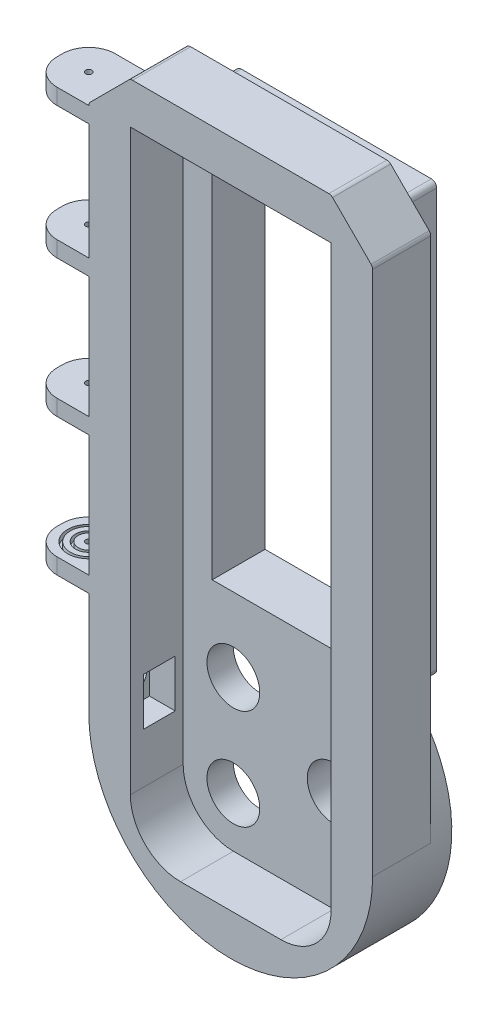
SolidWorks part; units mm, degrees
ref_plane "Alzado" through (0, 0, 0) normal (0, 0, 1) x (1, 0, 0)
ref_plane "Planta" through (0, 0, 0) normal (0, 1, 0) x (1, 0, 0)
ref_plane "Vista lateral" through (0, 0, 0) normal (1, 0, 0) x (0, 0, -1)
sketch "Croquis1" plane through (0, 0, 0) normal (0, 0, 1) x (1, 0, 0)
  line L1 (-19, -40.5) -> (19, -40.5)
  line L2 (-19, -40.5) -> (-19, 40.5)
  line L3 (-19, 40.5) -> (19, 40.5)
  line L4 (19, -40.5) -> (19, 40.5)
  line L5 (-19, -40.5) -> (19, 40.5) construction
  line L6 (-19, 40.5) -> (19, -40.5) construction
  line L7 (-19, -40.5) -> (19, -40.5)
  line L8 (-19, -40.5) -> (-19, -78.5)
  line L9 (-19, -78.5) -> (19, -78.5)
  line L10 (19, -40.5) -> (19, -78.5)
  line L13 (-13.5, 36) -> (13.5, 36)
  line L28 (13.5, 36) -> (13.5, -36)
  line L29 (-13.5, 36) -> (-13.5, -36)
  line L30 (-13.5, -36) -> (13.5, -36)
  circle A0 centre (-9.5, -50) radius 5
  circle A1 centre (9.5, -59.5) radius 5
  circle A2 centre (-9.5, -69) radius 5
  arc A3 (19, -40.5) -> (-19, -40.5) centre (0, -59.5) cw
  point P0 (0, 0)
  point P27 (9.5, -64.5)
  point P30 (9.5, -54.5)
  point P34 (-13.5, 0)
extrude "Saliente-Extruir1" add sketch "Croquis1" along normal blind 5 contours L1 L4 L3 L2 L30 L29 L13 L28 | L10 L1 L8 L9 A2 A1 A0 | A3 L10 | A3 L9 | A3 L8 region at (-18.1053, 0, 0) region at (0.6175, -59.5, 0) region at (-22.1912, -59.5, 0) region at (22.1912, -59.5, 0) region at (0, -81.6912, 0)
sketch "Croquis2" plane through (0, 0, 0) normal (0, 0, -1) x (-1, 0, 0)
  line L0 (-19, 40.5) -> (19, 40.5)
  line L1 (19, -40.5) -> (-19, -40.5)
  line L2 (-19, -40.5) -> (-19, 40.5)
  line L4 (19, -40.5) -> (19, 40.5)
  line L5 (-13.5, 36) -> (-13.5, -36)
  line L7 (-13.5, -36) -> (13.5, -36)
  line L8 (13.5, -36) -> (13.5, 36)
  line L9 (13.5, 36) -> (-13.5, 36)
extrude "Saliente-Extruir2" add sketch "Croquis2" along normal blind 5
sketch "Croquis3" plane through (0, 0, 5) normal (0, 0, 1) x (1, 0, 0)
  line L0 (26.8701, -59.5) -> (26.8701, 40.5)
  line L1 (19, -59.5) -> (19, 40.5)
  line L2 (19, 40.5) -> (-19, 40.5)
  line L3 (-19, 40.5) -> (-19, -59.5)
  line L4 (26.8701, 40.5) -> (19, 48.3701)
  line L5 (19, 48.3701) -> (-19, 48.3701)
  line L6 (-19, 48.3701) -> (-26.8701, 40.5)
  line L7 (-26.8701, 40.5) -> (-26.8701, -59.5)
  arc A2 (-19, -59.5) -> (19, -59.5) centre (0, -59.5) ccw
  arc A3 (-26.8701, -59.5) -> (26.8701, -59.5) centre (0, -59.5) ccw
extrude "Saliente-Extruir9" add sketch "Croquis3" against normal blind 1
sketch "Croquis4" plane through (0, 0, 4) normal (0, 0, -1) x (-1, 0, 0)
  line L0 (-19, 40.5) -> (-19, -40.5)
  line L1 (-19, 40.5) -> (19, 40.5)
  line L2 (19, 40.5) -> (19, -40.5)
  line L3 (14, -77) -> (-14, -77)
  line L4 (-19, -72) -> (-19, -41.338)
  line L5 (19, -72) -> (19, -40.5)
  line L6 (-26.8701, 40.5) -> (-19, 48.3701)
  line L7 (-19, 48.3701) -> (19, 48.3701)
  line L8 (19, 48.3701) -> (26.8701, 40.5)
  line L9 (26.8701, 40.5) -> (26.8701, -59.5)
  line L10 (-26.8701, 40.5) -> (-26.8701, -59.5)
  arc A0 (-19, -40.5) -> (-26.8701, -59.5) centre (0, -59.5) ccw construction
  arc A1 (-14, -77) -> (-19, -72) centre (-14, -72) cw
  arc A2 (14, -77) -> (19, -72) centre (14, -72) ccw
  arc A3 (-19, -40.5) -> (19, -40.5) centre (0, -59.5) ccw construction
  arc A4 (-26.8701, -59.5) -> (26.8701, -59.5) centre (0, -59.5) ccw
  arc M1 (19, -40.5) -> (26.8701, -59.5) centre (0, -59.5) cw
  line M2 (26.8701, -59.5) -> (26.8701, 40.5)
  line M3 (26.8701, 40.5) -> (19, 48.3701)
  line M4 (19, 48.3701) -> (-19, 48.3701)
  line M5 (-19, 48.3701) -> (-26.8701, 40.5)
  line M6 (-26.8701, 40.5) -> (-26.8701, -59.5)
  arc M7 (-26.8701, -59.5) -> (-19, -40.5) centre (0, -59.5) cw
  line M8 (-19, -40.5) -> (-19, 40.5)
  line M9 (-19, 40.5) -> (19, 40.5)
  line M10 (19, 40.5) -> (19, -40.5)
  dimension "D1" = 5
extrude "Saliente-Extruir10" add sketch "Croquis4" against normal blind 11 contours M10 M1 M2 M3 M4 M5 M6 M7 M8 M9 region at (20.2052, 0, 4)
sketch "Croquis5" plane through (0, 0, 5) normal (0, 0, 1) x (1, 0, 0)
  line L0 (-19, -59.5) -> (-19, -69)
  line L1 (19, -69) -> (19, -59.5)
  line L2 (9.5, -78.5) -> (-9.5, -78.5)
  line L3 (19, -59.5) -> (19, -40.5)
  line L4 (-19, -59.5) -> (-19, -40.5)
  arc A0 (-19, -40.5) -> (19, -40.5) centre (0, -59.5) ccw
  arc A1 (-9.5, -78.5) -> (-19, -69) centre (-9.5, -69) cw
  arc A2 (9.5, -78.5) -> (19, -69) centre (9.5, -69) ccw
extrude "Saliente-Extruir11" add sketch "Croquis5" along normal blind 10
fillet "Redondeo1" radius 1 4 edges at (-19, -40.5, -2.5) (-19, 40.5, -0.5) (19, 40.5, -0.5) (19, -40.5, -2.5)
fillet "Redondeo2" radius 1 5 edges at (-18.7071, 40.2071, 4) (18.7071, 40.2071, 4) (-19, -0.5, 4) (0, 40.5, 4) (19, -0.5, 4)
fillet "Redondeo3" radius 1 4 edges at (-26.8701, 40.5, 9.5) (-19, 48.3701, 9.5) (26.8701, 40.5, 9.5) (19, 48.3701, 9.5)
sketch "Croquis6" plane through (-26.8701, 0, 0) normal (-1, 0, 0) x (0, 0, 1)
  line L1 (4, -59.5) -> (15, -59.5) construction
  line L2 (6.5, -50.5) -> (12.5, -50.5)
  line L3 (12.5, -50.5) -> (12.5, -59.5)
  line L4 (12.5, -59.5) -> (6.5, -59.5)
  line L5 (6.5, -50.5) -> (6.5, -59.5)
extrude "Cortar-Extruir1" cut sketch "Croquis6" against normal blind 8
sketch "Croquis7" plane through (-26.8701, 0, 0) normal (-1, 0, 0) x (0, 0, 1)
  line L0 (6.5, -50.5) -> (12.5, -50.5)
  line L1 (12.5, -50.5) -> (12.5, -59.5)
  line L2 (12.5, -59.5) -> (6.5, -59.5)
  line L3 (6.5, -59.5) -> (6.5, -50.5)
  circle A0 centre (9.5, -55) radius 2.5
extrude "Saliente-Extruir12" add sketch "Croquis7" against normal blind 3
sketch "Croquis8" plane through (-26.8701, 0, 0) normal (-1, 0, 0) x (0, 0, 1)
  line L0 (4, 40.0858) -> (4, 37.0858)
  line L1 (4, 39.5) -> (4, -41.5556) construction
  line L2 (4, 37.0858) -> (15, 37.0858)
  line L3 (15, -59.5) -> (15, 40.0858) construction
  line L4 (15, 37.0858) -> (15, 40.0858)
  line L5 (15, 40.0858) -> (4, 40.0858)
  line L6 (9.5, 37.0858) -> (9.5, 15.0858)
  line L7 (9.5, 15.0858) -> (15, 15.0858)
  line L8 (9.5, 15.0858) -> (4, 15.0858)
  line L9 (4, 15.0858) -> (4, 12.0858)
  line L10 (4, 40.0858) -> (4, -59.5) construction
  line L11 (4, 12.0858) -> (15, 12.0858)
  line L12 (15, 12.0858) -> (15, 15.0858)
  line L13 (9.5, 12.0858) -> (9.5, -10.9142)
  line L14 (9.5, -10.9142) -> (15, -10.9142)
  line L15 (15, -10.9142) -> (15, -13.9142)
  line L16 (15, -13.9142) -> (4, -13.9142)
  line L17 (4, -13.9142) -> (4, -10.9142)
  line L18 (4, -10.9142) -> (9.5, -10.9142)
  line L19 (9.5, -13.9142) -> (9.5, -36.9142)
  line L20 (9.5, -36.9142) -> (15, -36.9142)
  line L21 (15, -36.9142) -> (15, -39.9142)
  line L22 (15, -39.9142) -> (4, -39.9142)
  line L23 (4, -39.9142) -> (4, -36.9142)
  line L24 (4, -36.9142) -> (9.5, -36.9142)
  line M2 (15, -59.5) -> (15, 40.0858)
  line M3 (15, 40.0858) -> (4, 40.0858)
  line M4 (4, 40.0858) -> (4, -59.5)
extrude "Saliente-Extruir13" add sketch "Croquis8" along normal blind 11 contours L2 M4 M2 M3 | L11 L7 L8 M4 M2 | L18 L16 L14 M4 M2 | L24 L22 L20 M4 M2 region at (-26.8701, 38.5858, 9.5) region at (-26.8701, 13.5858, 9.5) region at (-26.8701, -12.4142, 9.5) region at (-26.8701, -38.4142, 9.5)
fillet "Redondeo4" radius 5 8 edges at (-37.8701, -38.4142, 4) (-37.8701, -38.4142, 15) (-37.8701, -12.4142, 4) (-37.8701, -12.4142, 15) (-37.8701, 13.5858, 4) (-37.8701, 13.5858, 15) (-37.8701, 38.5858, 4) (-37.8701, 38.5858, 15)
sketch "Croquis9" plane through (0, 40.0858, 0) normal (0, 1, 0) x (1, 0, 0)
  circle A0 centre (-32.3701, -9.5) radius 0.6
extrude "Cortar-Extruir2" cut sketch "Croquis9" against normal blind 80
sketch "Croquis10" plane through (0, -39.9142, 0) normal (0, -1, 0) x (1, 0, 0)
  circle A0 centre (-32.3701, 9.5) radius 0.6
extrude "Saliente-Extruir14" add sketch "Croquis10" against normal blind 2
sketch "Croquis11" plane through (0, -36.9142, 0) normal (0, 1, 0) x (1, 0, 0)
  circle A0 centre (-32.3701, -9.5) radius 2
  circle A1 centre (-32.3701, -9.5) radius 2.5
  circle A2 centre (-32.3701, -9.5) radius 3.5
  circle A3 centre (-32.3701, -9.5) radius 4
extrude "Cortar-Extruir3" cut sketch "Croquis11" against normal blind 1 contours A3 A2 | A1 A0 region at (-34.7993, -36.9142, 9.5) region at (-36.2569, -36.9142, 9.5)
